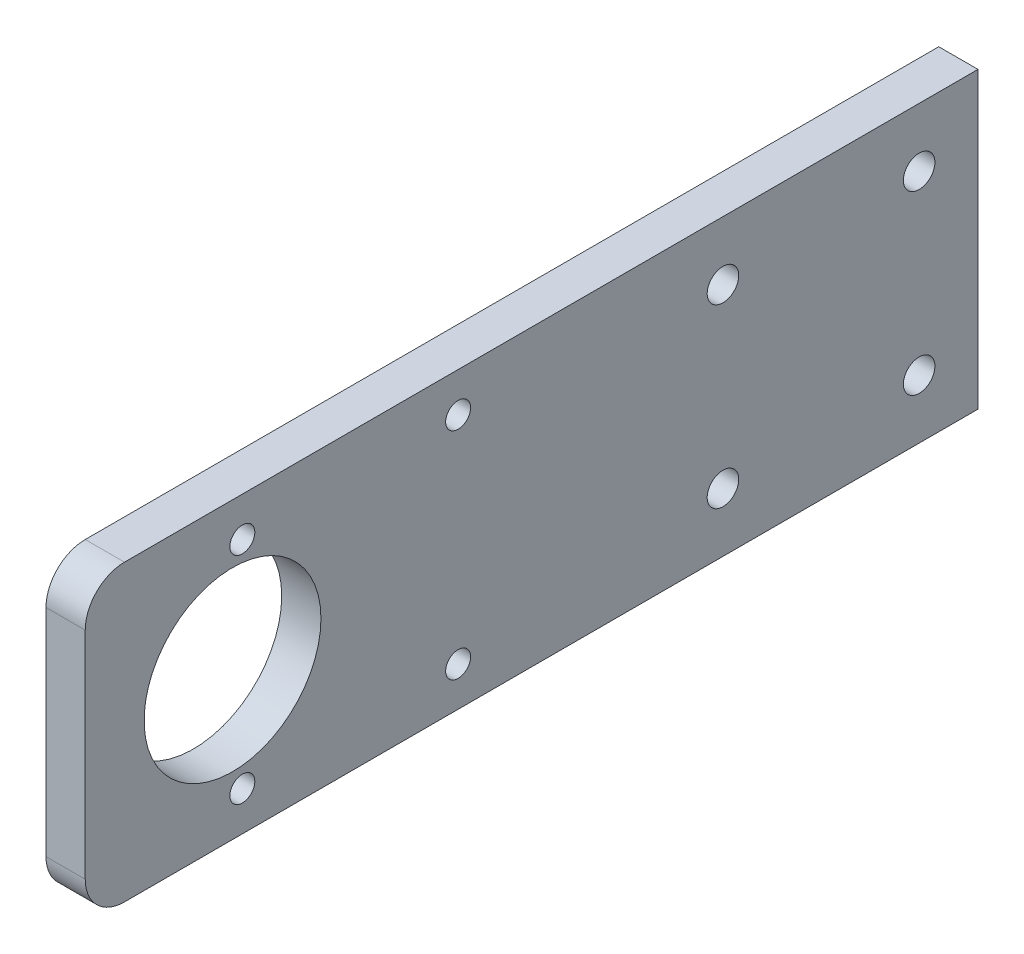
SolidWorks part; units mm, degrees
material "6061-T6 (SS)"
ref_plane "Front" through (0, 0, 0) normal (0, 0, 1) x (1, 0, 0)
ref_plane "Top" through (0, 0, 0) normal (0, 1, 0) x (1, 0, 0)
ref_plane "Right" through (0, 0, 0) normal (1, 0, 0) x (0, 0, -1)
sketch "Sketch1" plane through (0, 0, 0) normal (1, 0, 0) x (0, 0, -1)
  line L0 (0, -23.8125) -> (0, 23.8125)
  line L3 (0, 23.8125) -> (-144.4879, 23.8125)
  line L4 (-144.4879, -23.8125) -> (0, -23.8125)
  line L5 (-144.4879, 23.8125) -> (-144.4879, -23.8125)
  line L6 (-120.65, 23.8125) -> (-120.65, -23.8125) construction
  circle A1 centre (-120.65, 0) radius 14.3129
  point P4 (0, 0)
  dimension "D3" = 28.6258
  dimension "D1" = 9.525
  dimension "D2" = 47.625
  dimension "D5" = 120.65
extrude "Boss-Extrude1" add sketch "Sketch1" along normal blind 6.35
fillet "Fillet1" radius 6.35 2 edges at (3.175, -23.8125, 144.4879) (3.175, 23.8125, 144.4879)
sketch "Sketch4" plane through (0, 0, 0) normal (-1, 0, 0) x (0, 0, 1)
  point P0 (84.1375, 17.4625)
  point P3 (119.0625, 17.4625)
  point P6 (119.0625, -17.4625)
  point P9 (84.1375, -17.4625)
hole_wizard "#10-32 Tapped Hole1" positions "Sketch4" profile "Sketch3" tap size "#10-32" standard "ANSI Inch" end condition up to next
sketch "Sketch3" plane through (0, 17.4625, 84.1375) normal (0, 1, 0) x (0, 0, 1)
  line L0 (0, 0) -> (0, 6.35)
  line L1 (0, 6.35) -> (2.0193, 6.35)
  line L2 (2.0193, 6.35) -> (2.0193, 0)
  line L5 (2.0193, 0) -> (0, 0)
  line L11 (0, -6.35) -> (0, 107.95) construction
  dimension "Thru Tap Drill Dia." = 4.0386
  dimension "Thru Tap Drill Depth" = 6.35
cosmetic thread "Hole Thread1" parameters "D2"=4.826
cosmetic thread "Hole Thread2" parameters "D2"=4.826
cosmetic thread "Hole Thread3" parameters "D2"=4.826
cosmetic thread "Hole Thread4" parameters "D2"=4.826
sketch "Sketch7" plane through (6.35, 0, 0) normal (1, 0, 0) x (0, 0, -1)
  line L0 (-50.8, 23.8125) -> (-50.8, -23.8125) construction
  line L1 (0, 23.8125) -> (-138.1379, 23.8125) construction
  line L2 (-138.1379, -23.8125) -> (0, -23.8125) construction
  line L4 (0, -23.8125) -> (0, 23.8125) construction
  point P0 (-9.525, 14.2875)
  point P2 (-41.275, 14.2875)
  point P4 (-41.275, -14.2875)
  point P6 (-9.525, -14.2875)
  dimension "D1" = 50.8
  dimension "D2" = 9.525
  dimension "D3" = 9.525
  dimension "D4" = 9.525
  dimension "D5" = 9.525
hole_wizard "#10 Clearance Hole1" positions "Sketch7" profile "Sketch6" hole size "#10" standard "ANSI Inch" end condition up to next
sketch "Sketch6" plane through (6.35, 14.2875, 9.525) normal (0, 1, 0) x (0, 0, -1)
  line L0 (0, 0) -> (0, 6.35)
  line L1 (0, 6.35) -> (2.5527, 6.35)
  line L2 (2.5527, 6.35) -> (2.5527, 0)
  line L5 (2.5527, 0) -> (0, 0)
  line L11 (0, -6.35) -> (0, 107.95) construction
  dimension "Thru Hole Dia." = 5.1054
  dimension "Thru Hole Depth" = 6.35
